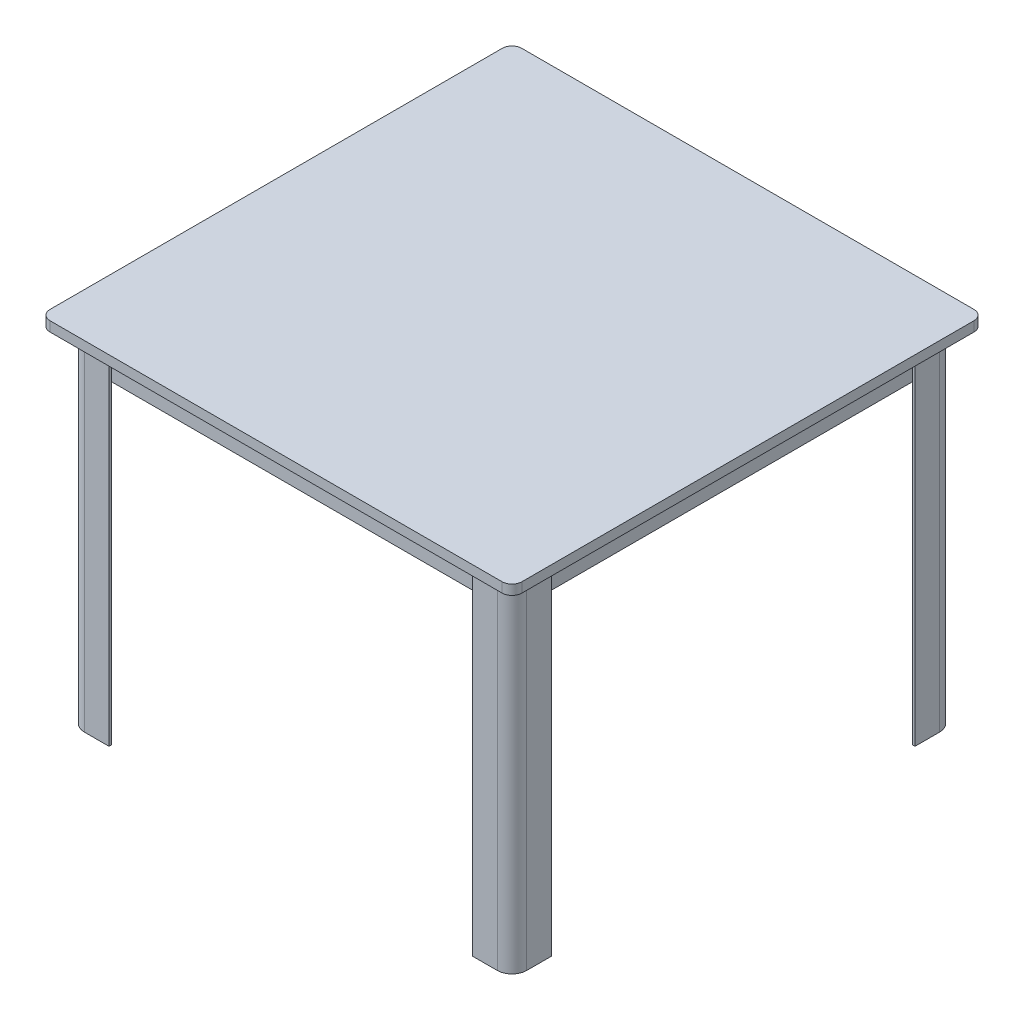
SolidWorks part; units mm, degrees
ref_plane "Front Plane" through (0, 0, 0) normal (0, 0, 1) x (1, 0, 0)
ref_plane "Top Plane" through (0, 0, 0) normal (0, 1, 0) x (1, 0, 0)
ref_plane "Right Plane" through (0, 0, 0) normal (1, 0, 0) x (0, 0, -1)
sketch "Sketch1" plane through (0, 0, 0) normal (0, 1, 0) x (1, 0, 0)
  line L0 (0, -609.6) -> (0, 609.6) construction
  line L1 (-609.6, -609.6) -> (609.6, -609.6)
  line L2 (-609.6, -609.6) -> (-609.6, 609.6)
  line L3 (-609.6, 609.6) -> (609.6, 609.6)
  line L4 (609.6, -609.6) -> (609.6, 609.6)
  line L5 (-609.6, 0) -> (609.6, 0) construction
  point P9 (0, 0)
  dimension "D1" = 1219.2
  dimension "D2" = 1219.2
extrude "Extrude1" add sketch "Sketch1" against normal blind 25.4
fillet "Fillet1" radius 25.4 4 edges at (-609.6, -12.7, 609.6) (609.6, -12.7, -609.6) (-609.6, -12.7, -609.6) (609.6, -12.7, 609.6)
sketch "Sketch2" plane through (0, -25.4, 0) normal (0, -1, 0) x (1, 0, 0)
  line L0 (-584.2, 609.6) -> (584.2, 609.6) construction
  line L1 (-609.6, -584.2) -> (-609.6, 584.2) construction
  line L8 (-469.9, 571.5) -> (-469.9, 565.15)
  line L13 (-571.5, 469.9) -> (-565.15, 469.9)
  line L14 (-533.4, 571.5) -> (-469.9, 571.5)
  line L15 (-533.4, 565.15) -> (-469.9, 565.15)
  line L16 (-565.15, 533.4) -> (-565.15, 469.9)
  line L17 (-571.5, 533.4) -> (-571.5, 469.9)
  arc A0 (-571.5, 533.4) -> (-533.4, 571.5) centre (-533.4, 533.4) cw
  arc A1 (-565.15, 533.4) -> (-533.4, 565.15) centre (-533.4, 533.4) cw
  dimension "D9" = 38.1
  dimension "D10" = 31.75
  dimension "D2" = 38.1
  dimension "D3" = 38.1
  dimension "D4" = 6.35
  dimension "D5" = 6.35
  dimension "D6" = 101.6
  dimension "D7" = 101.6
extrude "Extrude2" add sketch "Sketch2" along normal blind 889
sketch "Sketch3" plane through (0, -25.4, 0) normal (0, -1, 0) x (1, 0, 0)
  line L0 (-565.15, 533.4) -> (-565.15, -533.4)
  line L1 (-565.15, -533.4) -> (-558.8, -533.4)
  line L2 (-558.8, -533.4) -> (-558.8, 533.4)
  line L3 (-558.8, 533.4) -> (-565.15, 533.4)
  dimension "D1" = 6.35
  dimension "D2" = 1066.8
extrude "Extrude3" add sketch "Sketch3" along normal blind 76.2
ref_axis "Axis1" through (0, 0, 0) along (0, -1, 0)
pattern_circular "CirPattern1" count 4 over 360 about axis through (0, 0, 0) along (0, -1, 0) of "Extrude2", "Extrude3"
